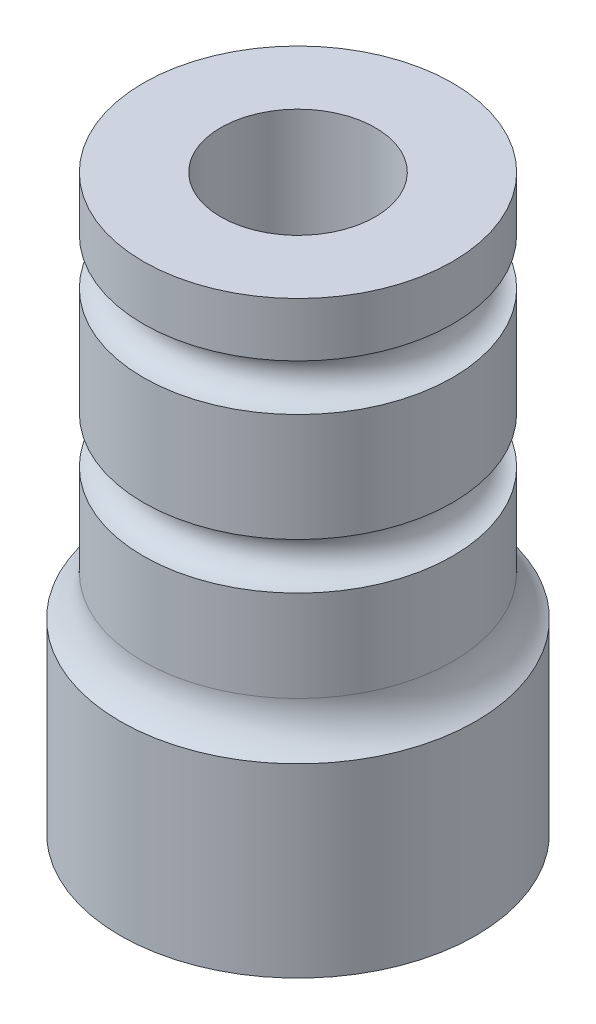
SolidWorks part; units mm, degrees
ref_plane "Спереди" through (0, 0, 0) normal (0, 0, 1) x (1, 0, 0)
ref_plane "Сверху" through (0, 0, 0) normal (0, 1, 0) x (1, 0, 0)
ref_plane "Справа" through (0, 0, 0) normal (1, 0, 0) x (0, 0, -1)
sketch "Эскиз1" plane through (0, 0, 0) normal (0, 1, 0) x (1, 0, 0)
  circle A0 centre (0, 0) radius 8
  circle A1 centre (0, 0) radius 11.5
  dimension "D1" = 16
  dimension "D2" = 23
extrude "Вытянуть1" add sketch "Эскиз1" along normal blind 8
sketch "Эскиз2" plane through (0, 8, 0) normal (0, 1, 0) x (1, 0, 0)
  circle A0 centre (0, 0) radius 11.5
  dimension "D1" = 23
extrude "Вытянуть2" add sketch "Эскиз2" along normal blind 4
sketch "Эскиз3" plane through (0, 7.9797, 0) normal (0, 1, 0) x (1, 0, 0)
  circle A0 centre (-1.4884, -5.9722) radius 1.5
  circle A1 centre (1.4884, 5.9722) radius 1.5
extrude "Вырез-Вытянуть1" cut sketch "Эскиз3" along normal blind 2.2
sketch "Эскиз4" plane through (0, 12, 0) normal (0, 1, 0) x (1, 0, 0)
  circle A0 centre (0, 0) radius 5
  circle A1 centre (0, 0) radius 10
  dimension "D1" = 10
  dimension "D2" = 20
extrude "Вытянуть3" add sketch "Эскиз4" along normal blind 25
fillet "Скругление1" radius 3 1 edges at (0, 12, 10)
sketch "Эскиз5" plane through (0, 0, 0) normal (1, 0, 0) x (0, 0, -1)
  line L1 (-10, 37) -> (-10, 14.5981) construction
  circle A0 centre (-9.9941, 22) radius 1.5
  circle A1 centre (-10, 32) radius 1.5
  dimension "D1" = 3
  dimension "D2" = 3
  dimension "D3" = 9.9941
  dimension "D4" = 22
  dimension "D5" = 32
ref_plane "Плоскость1" through (0, 32, 0) normal (0, 1, 0) x (-1, 0, 0)
sketch "Эскиз7" plane through (0, 32, 0) normal (0, 1, 0) x (-1, 0, 0)
  circle A0 centre (0, 0) radius 10
sweep "Вырез-По траектории2" cut profiles "Эскиз5" path "Эскиз7"
